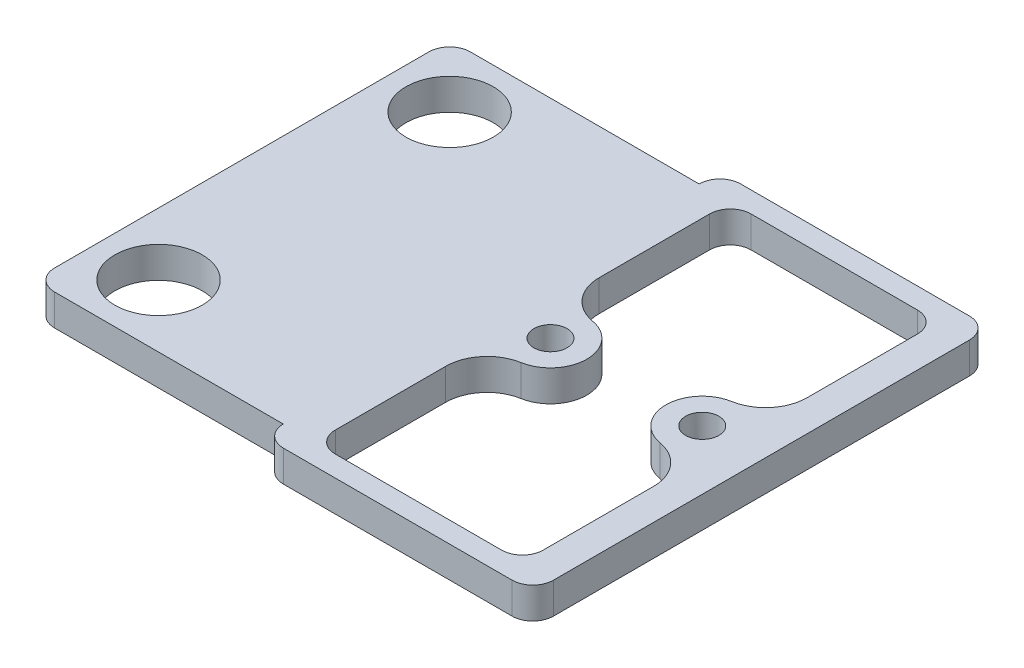
SolidWorks part; units mm, degrees
material "ABS"
ref_plane "前视基准面" through (0, 0, 0) normal (0, 0, 1) x (1, 0, 0)
ref_plane "上视基准面" through (0, 0, 0) normal (0, 1, 0) x (1, 0, 0)
ref_plane "右视基准面" through (0, 0, 0) normal (1, 0, 0) x (0, 0, -1)
sketch "草图1" plane through (0, 0, 0) normal (0, 1, 0) x (1, 0, 0)
  line L1 (-6.5, -11) -> (6.5, -11)
  line L2 (-6.5, -11) -> (-6.5, 11)
  line L3 (-6.5, 11) -> (6.5, 11)
  line L4 (6.5, -11) -> (6.5, 11)
  line L5 (-6.5, -11) -> (6.5, 11) construction
  line L6 (-6.5, 11) -> (6.5, -11) construction
  line L7 (-17.5, -3) -> (17.5, -3)
  line L8 (-17.5, -3) -> (-17.5, 3)
  line L9 (-17.5, 3) -> (17.5, 3)
  line L10 (17.5, -3) -> (17.5, 3)
  line L11 (-17.5, -3) -> (17.5, 3) construction
  line L12 (-17.5, 3) -> (17.5, -3) construction
  point P0 (0, 0)
  point P6 (0, 0)
  dimension "D1" = 13
  dimension "D2" = 22
  dimension "D3" = 6
  dimension "D4" = 35
extrude "凸台-拉伸1" add sketch "草图1" along normal blind 1.5 contours L9 L8 L7 L2 | L7 L2 L1 L4 | L9 L2 L7 L4 | L2 L9 L4 L3 | L7 L10 L9 L4 region at (0, 0, 7) region at (-12, 0, 0) region at (0, 0, 0) region at (12, 0, 0) region at (0, 0, -7)
sketch "草图2" plane through (0, 1.5, 0) normal (0, 1, 0) x (1, 0, 0)
  line L0 (0, 0) -> (-3.65, 0) construction
  line L1 (-5, -10) -> (5, -10)
  line L2 (-5, -10) -> (-5, -1.1136)
  line L3 (-5, 10) -> (5, 10)
  line L4 (5, -10) -> (5, -1.1136)
  line L5 (-5, -10) -> (5, 10) construction
  line L6 (-5, 10) -> (5, -10) construction
  line L7 (-5, 1.1136) -> (-5, 10)
  line L8 (0, 0) -> (0, -10) construction
  line L9 (5, 1.1136) -> (5, 10)
  arc A1 (-5, -1.1136) -> (-5, 1.1136) centre (-3.65, 0) ccw
  arc A2 (5, -1.1136) -> (5, 1.1136) centre (3.65, 0) cw
  point P0 (0, 0)
  dimension "D3" = 3.65
  dimension "D4" = 3.5
  dimension "D1" = 10
  dimension "D2" = 20
extrude "切除-拉伸1" cut sketch "草图2" against normal blind 1.5
fillet "圆角1" radius 2 4 edges at (5, 0.75, -1.1136) (5, 0.75, 1.1136) (-5, 0.75, 1.1136) (-5, 0.75, -1.1136)
fillet "圆角2" radius 1 16 edges at (-17.5, 0.75, -3) (-17.5, 0.75, 3) (-6.5, 0.75, 3) (-6.5, 0.75, 11) (6.5, 0.75, 11) (6.5, 0.75, 3) (17.5, 0.75, 3) (17.5, 0.75, -3) (6.5, 0.75, -3) (6.5, 0.75, -11) (-6.5, 0.75, -11) (-6.5, 0.75, -3) (5, 0.75, 10) (-5, 0.75, 10) (5, 0.75, -10) (-5, 0.75, -10)
sketch "草图3" plane through (0, 1.5, 0) normal (0, 1, 0) x (1, 0, 0)
  line L0 (0, 0) -> (0, 4.3185) construction
  circle A0 centre (-3.65, 0) radius 0.8
  circle A1 centre (3.65, 0) radius 0.8
  dimension "D1" = 1.6
extrude "切除-拉伸2" cut sketch "草图3" against normal blind 10
sketch "草图4" plane through (0, 1.5, 0) normal (0, 1, 0) x (1, 0, 0)
  line L0 (-6.5, -4) -> (-6.5, 4)
  line L2 (6.5, -4) -> (6.5, 4)
  line L3 (-5, 9) -> (-5, 3.6932) construction
  line L4 (4, 10) -> (-4, 10) construction
  line L5 (5, 3.6932) -> (5, 9) construction
  line L6 (5, -9) -> (5, -3.6932) construction
  line L7 (-4, -10) -> (4, -10) construction
  line L8 (-5, -3.6932) -> (-5, -9) construction
  line L9 (5, -3.6932) -> (5, 9)
  line L10 (5, -9) -> (5, -3.6932)
  line L11 (-4, -10) -> (4, -10)
  line L12 (-5, -3.6932) -> (-5, -9)
  line L13 (-17.5, 2) -> (-17.5, -2)
  line L14 (-7.5, 3) -> (-16.5, 3)
  line L15 (-6.5, 10) -> (-6.5, 4)
  line L16 (5.5, 11) -> (-5.5, 11)
  line L17 (6.5, 4) -> (6.5, 10)
  line L18 (16.5, 3) -> (7.5, 3)
  line L19 (17.5, -2) -> (17.5, 2)
  line L20 (7.5, -3) -> (16.5, -3)
  line L21 (6.5, -10) -> (6.5, -4)
  line L22 (-5.5, -11) -> (5.5, -11)
  line L23 (-6.5, -4) -> (-6.5, -10)
  line L24 (-16.5, -3) -> (-7.5, -3)
  line L27 (-6.5, 10) -> (-6.5, 4)
  line L28 (5.5, 11) -> (-5.5, 11)
  line L29 (6.5, 4) -> (6.5, 10)
  line L33 (6.5, -10) -> (6.5, -4)
  line L34 (-5.5, -11) -> (5.5, -11)
  line L35 (-6.5, -4) -> (-6.5, -10)
  line L37 (-5, 9) -> (-5, -3.6932)
  line L38 (4, 10) -> (-4, 10)
  arc A0 (-4, 10) -> (-5, 9) centre (-4, 9) ccw construction
  arc A4 (4, -10) -> (5, -9) centre (4, -9) ccw construction
  arc A5 (-5, -9) -> (-4, -10) centre (-4, -9) ccw construction
  arc A9 (5, 9) -> (4, 10) centre (4, 9) ccw construction
  arc A12 (-16.5, 3) -> (-17.5, 2) centre (-16.5, 2) ccw
  arc A13 (-7.5, 3) -> (-6.5, 4) centre (-7.5, 4) ccw
  arc A14 (-5.5, 11) -> (-6.5, 10) centre (-5.5, 10) ccw
  arc A15 (6.5, 10) -> (5.5, 11) centre (5.5, 10) ccw
  arc A16 (6.5, 4) -> (7.5, 3) centre (7.5, 4) ccw
  arc A17 (17.5, 2) -> (16.5, 3) centre (16.5, 2) ccw
  arc A18 (16.5, -3) -> (17.5, -2) centre (16.5, -2) ccw
  arc A19 (7.5, -3) -> (6.5, -4) centre (7.5, -4) ccw
  arc A20 (5.5, -11) -> (6.5, -10) centre (5.5, -10) ccw
  arc A21 (-6.5, -10) -> (-5.5, -11) centre (-5.5, -10) ccw
  arc A22 (-6.5, -4) -> (-7.5, -3) centre (-7.5, -4) ccw
  arc A23 (-17.5, -2) -> (-16.5, -3) centre (-16.5, -2) ccw
  arc A26 (-5.5, 11) -> (-6.5, 10) centre (-5.5, 10) ccw
  arc A27 (6.5, 10) -> (5.5, 11) centre (5.5, 10) ccw
  arc A32 (5.5, -11) -> (6.5, -10) centre (5.5, -10) ccw
  arc A33 (-6.5, -10) -> (-5.5, -11) centre (-5.5, -10) ccw
  arc A37 (4, -10) -> (5, -9) centre (4, -9) ccw
  arc A38 (-5, -9) -> (-4, -10) centre (-4, -9) ccw
  arc A42 (-4, 10) -> (-5, 9) centre (-4, 9) ccw
  arc A43 (5, 9) -> (4, 10) centre (4, 9) ccw
  dimension "D1" = 0
sketch "草图5" plane through (0, 0, 0) normal (0, -1, 0) x (1, 0, 0)
  line L0 (-17.5, 0) -> (17.5, 0) construction
  line L1 (-17.5, 2) -> (-17.5, -2) construction
  line L2 (17.5, 2) -> (17.5, -2) construction
  line L3 (0, 0) -> (0, -10) construction
  line L4 (4, -10) -> (-4, -10) construction
  circle A0 centre (-13, 0) radius 1.55
  circle A1 centre (13, 0) radius 1.55
  dimension "D1" = 3.1
  dimension "D2" = 26
extrude "切除-拉伸3" cut sketch "草图5" against normal blind 10
sketch "草图6" plane through (0, 1.5, 0) normal (0, 1, 0) x (1, 0, 0)
sketch "草图7" plane through (0, 1.5, 0) normal (0, 1, 0) x (1, 0, 0)
  line L0 (6.5, -4) -> (6.5, 4)
  line L1 (6.5, 4) -> (17.5052, 4)
  line L2 (17.5052, 4) -> (17.5052, -4)
  line L3 (17.5052, -4) -> (6.5, -4)
extrude "切除-拉伸4" cut sketch "草图7" against normal blind 10
sketch "草图8" plane through (-6.5, 0, 0) normal (-1, 0, 0) x (0, 0, 1)
  line L0 (-4, 1.5) -> (-4, 0)
  line L1 (-4, 0) -> (4, 0)
  line L2 (4, 0) -> (4, 1.5)
  line L3 (4, 1.5) -> (-4, 1.5)
sketch "草图9" plane through (-6.5, 0, 0) normal (-1, 0, 0) x (0, 0, 1)
  line L0 (-10, 1.5) -> (-10, 0)
sketch "草图10" plane through (-6.5, 0, 0) normal (-1, 0, 0) x (0, 0, 1)
  line L0 (-4, 1.5) -> (-4, 0)
  line L1 (-4, 0) -> (4, 0)
  line L2 (4, 0) -> (4, 1.5)
  line L3 (4, 1.5) -> (-4, 1.5)
extrude "切除-拉伸7" cut sketch "草图10" along normal blind 13
sketch "草图11" plane through (0, 1.5, 0) normal (0, 1, 0) x (1, 0, 0)
  line L0 (-6.5, 10) -> (-6.5, 4)
  line L1 (-6.5, 10) -> (-18.5, 10)
  line L2 (-6.5, 4) -> (-18.5, 4)
  line L3 (-18.5, 10) -> (-18.5, 4)
  line L4 (-6.5, -4) -> (-6.5, -10)
  line L5 (-6.5, -4) -> (-18.5, -4)
  line L6 (-6.5, -10) -> (-18.5, -10)
  line L7 (-18.5, -4) -> (-18.5, -10)
  dimension "D1" = 12
  dimension "D2" = 12
extrude "凸台-拉伸3" add sketch "草图11" against normal up to surface (1.5 mm away) contours L0 L1 L3 L2 | L4 L5 L7 L6 up to face at (0, 0, 0)
sketch "Sketch2" plane through (0, 0, 0) normal (0, -1, 0) x (1, 0, 0)
  line L1 (-6.5, 4) -> (-18.5, 4)
  line L2 (-6.5, 4) -> (-6.5, -4)
  line L3 (-6.5, -4) -> (-18.5, -4)
  line L4 (-18.5, 4) -> (-18.5, -4)
extrude "Boss-Extrude1" add sketch "Sketch2" against normal up to surface (1.5 mm away) up to face at (0, 1.5, 0)
sketch "Sketch3" plane through (0, 1.5, 0) normal (0, 1, 0) x (1, 0, 0)
  circle A0 centre (-15.5, -7) radius 2.1
  circle A1 centre (-15.5, 7) radius 2.1
  dimension "D1" = 4.2
  dimension "D2" = 4.2
extrude "Cut-Extrude1" cut sketch "Sketch3" against normal blind 10
fillet "Fillet1" radius 1 2 edges at (-18.5, 0.75, 10) (-18.5, 0.75, -10)
